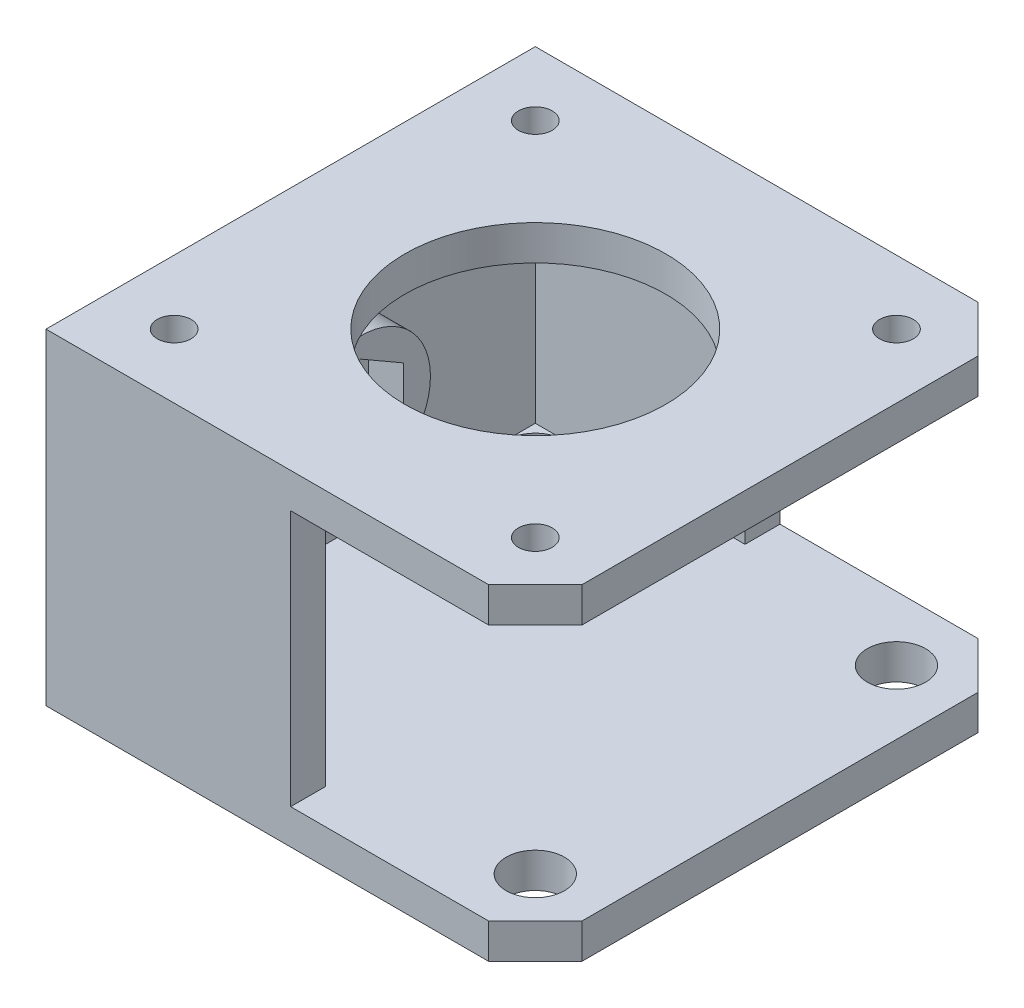
SolidWorks part; units mm, degrees
ref_plane "Front Plane" through (0, 0, 0) normal (0, 0, 1) x (1, 0, 0)
ref_plane "Top Plane" through (0, 0, 0) normal (0, 1, 0) x (1, 0, 0)
ref_plane "Right Plane" through (0, 0, 0) normal (1, 0, 0) x (0, 0, -1)
sketch "Sketch1" plane through (0, 0, 0) normal (0, 1, 0) x (1, 0, 0)
  line L0 (0, 21) -> (0, 18)
  line L1 (-21, -21) -> (21, -21)
  line L2 (-21, -21) -> (-21, 21)
  line L3 (-21, 21) -> (21, 21)
  line L4 (21, -21) -> (21, 21)
  line L5 (-21, -21) -> (21, 21) construction
  line L6 (-21, 21) -> (21, -21) construction
  line L7 (-18, -18) -> (18, -18)
  line L8 (-18, -18) -> (-18, 18)
  line L9 (-18, 18) -> (18, 18)
  line L10 (18, -18) -> (18, 18)
  line L11 (-18, -18) -> (18, 18) construction
  line L12 (-18, 18) -> (18, -18) construction
  line L13 (0, -18) -> (0, -21)
  circle A0 centre (0, 0) radius 11.2
  circle A1 centre (-15.5, 15.5) radius 1.45
  circle A2 centre (15.5, 15.5) radius 1.45
  circle A3 centre (15.5, -15.5) radius 1.45
  circle A4 centre (-15.5, -15.5) radius 1.45
  point P0 (0, 0)
  point P6 (0, 0)
  point P24 (0, 0)
  dimension "D3" = 22.4
  dimension "D4" = 2.9
  dimension "D1" = 42
  dimension "D2" = 3
  dimension "D6" = 31
  dimension "D5" = 4
extrude "Boss-Extrude1" add sketch "Sketch1" along normal blind 3 contours L1 L4 L3 L2 L10 L7 L8 L9 | L7 L10 L9 L8 A4 A3 A2 A1 A0 | L13 L7 L8 L9 L0 L3 L2 L1 region at (10.5, 0, -20.5304) region at (-0.4696, 0, -19.5) region at (9, 0, -17.4909)
extrude "Boss-Extrude2" add sketch "Sketch1<3>" against normal blind 25 contours L13 L7 L8 L9 L0 L3 L2 L1 region at (-0.4696, 0, -19.5)
sketch "Sketch1<3>" plane through (0, 0, 0) normal (0, 1, 0) x (1, 0, 0) same geometry as "Sketch1"
extrude "Boss-Extrude3" add sketch "Sketch1<4>" along normal blind 3 from surface contours L13 L7 L8 L9 L0 L3 L2 L1 | L7 L13 L1 L4 L3 L0 L9 L10 | L7 L10 L9 L8 A4 A3 A2 A1 A0 | A4 | A3 | A0 | A1 | A2 region at (10.5, 0, -20.5304) region at (-0.4696, 0, -19.5) region at (9, 0, -17.4909) region at (0, 0, 0) region at (-15.5, 0, -15.5) region at (15.5, 0, -15.5) region at (15.5, 0, 15.5) region at (-15.5, 0, 15.5) starting at face at (-9.75, -25, 0)
sketch "Sketch1<4>" plane through (0, 0, 0) normal (0, 1, 0) x (1, 0, 0) same geometry as "Sketch1"
sketch "Sketch3" plane through (-18, 0, 0) normal (1, 0, 0) x (0, 0, -1)
  line L0 (-18, -11) -> (18, -11) construction
  line L1 (-18, -22) -> (-18, 0) construction
  line L2 (18, -22) -> (18, 0) construction
  line L3 (18, -22) -> (18, 0) construction
  line L4 (0, -6.7276) -> (-3.7, -8.8638)
  line L5 (-3.7, -8.8638) -> (-3.7, -13.1362)
  line L6 (-3.7, -13.1362) -> (0, -15.2724)
  line L7 (0, -15.2724) -> (3.7, -13.1362)
  line L8 (3.7, -13.1362) -> (3.7, -8.8638)
  line L9 (3.7, -8.8638) -> (0, -6.7276)
  circle A0 centre (0, -11) radius 2.2
  circle A1 centre (0, -11) radius 3.7 construction
  circle A2 centre (0, -11) radius 6
  dimension "D1" = 4.4
  dimension "D3" = 12
  dimension "D2" = 7.4
extrude "Cut-Extrude1" cut sketch "Sketch3" against normal through all contours A0 region at (-18, -11, 0)
extrude "Boss-Extrude4" add sketch "Sketch3<3>" along normal blind 3 contours A2 L9 L8 L7 L6 L5 L4 region at (-18, -11, 5.8303)
sketch "Sketch3<3>" plane through (-18, 0, 0) normal (1, 0, 0) x (0, 0, -1) same geometry as "Sketch3"
sketch "Sketch2" plane through (0, -22, 0) normal (0, 1, 0) x (1, 0, 0)
  circle A1 centre (15.5, 15.5) radius 2.5
  circle A2 centre (15.5, -15.5) radius 2.5
  circle A3 centre (-15.5, -15.5) radius 2.5
  circle A4 centre (-15.5, 15.5) radius 2.5
  point P2 (0, 0)
  point P3 (0, 0)
  point P13 (0, 0)
  dimension "D1" = 5
  dimension "D2" = 4
extrude "Cut-Extrude2" cut sketch "Sketch2" against normal through all
chamfer "Chamfer1" distance 4 4 edges at (21, 1.5, -21) (21, -23.5, -21) (21, -23.5, 21) (21, 1.5, 21)
